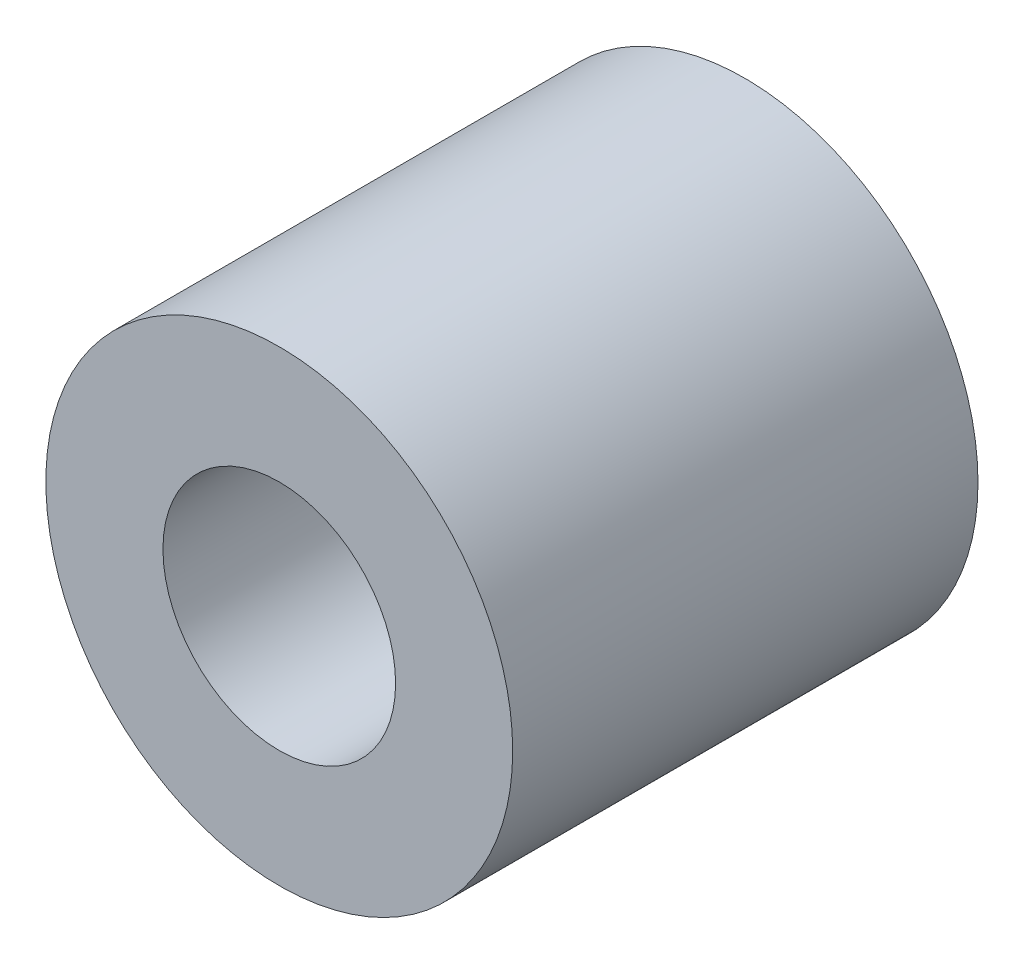
SolidWorks part; units mm, degrees
material "Brass"
ref_plane "Front Plane" through (0, 0, 0) normal (0, 0, 1) x (1, 0, 0)
ref_plane "Top Plane" through (0, 0, 0) normal (0, 1, 0) x (1, 0, 0)
ref_plane "Right Plane" through (0, 0, 0) normal (1, 0, 0) x (0, 0, -1)
sketch "Sketch1" plane through (0, 0, 0) normal (0, 0, 1) x (1, 0, 0)
  circle A0 centre (0, 0) radius 3.01
  circle A1 centre (0, 0) radius 1.5
  dimension "D1" = 6.02
  dimension "ID" = 3
extrude "Extrude1" add sketch "Sketch1" along normal mid plane 6
sketch "Sketch2" plane through (0, 0, 0) normal (1, 0, 0) x (0, 0, -1)
  line L0 (-3, -1.5) -> (3, -1.5) construction
  line L3 (3, 1.5) -> (-3, 1.5) construction
  line L5 (-3, -1.5) -> (3, -1.5)
  line L6 (3, 1.5) -> (-3, 1.5)
sketch "Sketch4" plane through (0, 0, 3) normal (0, 0, 1) x (1, 0, 0)
  line L0 (0, 0) -> (-1.0607, 1.0607)
  line L1 (0, -3.3) -> (0, 3.3) construction
  circle A0 centre (0, 0) radius 1.5 construction
  dimension "D1" = 45
ref_axis "Center Axis 1" through (0, 0, -22) along (0, 0, 1)
ref_plane "Contaxt Plane 1" through (0, 0, 3) normal (0, 0, 1) x (1, 0, 0)
ref_plane "Contact Plane 2" through (0, 0, -3) normal (0, 0, -1) x (-1, 0, 0)
